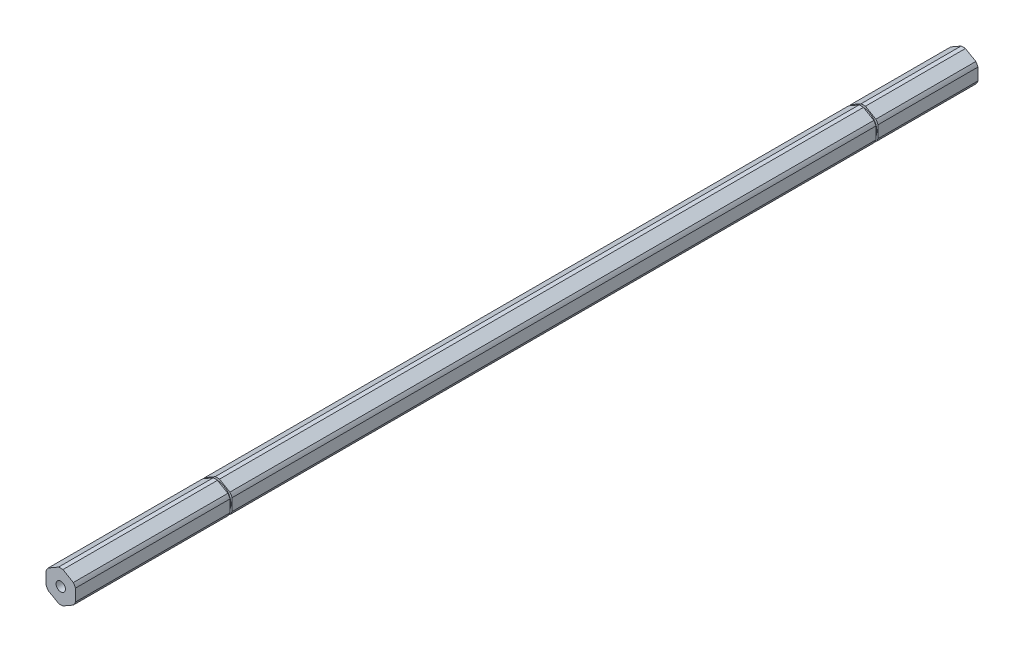
SolidWorks part; units mm, degrees
material "6061-T6 (SS)"
ref_plane "Front Plane" through (0, 0, 0) normal (0, 0, 1) x (1, 0, 0)
ref_plane "Top Plane" through (0, 0, 0) normal (0, 1, 0) x (1, 0, 0)
ref_plane "Right Plane" through (0, 0, 0) normal (1, 0, 0) x (0, 0, -1)
sketch "Sketch1" plane through (0, 0, 0) normal (0, 0, 1) x (1, 0, 0)
  line L1 (0, 7.3323) -> (-6.35, 3.6662)
  line L2 (-6.35, 3.6662) -> (-6.35, -3.6662)
  line L3 (-6.35, -3.6662) -> (0, -7.3323)
  line L4 (0, -7.3323) -> (6.35, -3.6662)
  line L5 (6.35, -3.6662) -> (6.35, 3.6662)
  line L6 (6.35, 3.6662) -> (0, 7.3323)
  circle A0 centre (0, 0) radius 6.35 construction
  circle A1 centre (0, 0) radius 6.858
  dimension "D1" = 12.7
  dimension "D2" = 13.716
extrude "Boss-Extrude1" add sketch "Sketch1" along normal mid plane 388.6403 contours L5 A1 L6 L1 L2 L3 L4 region at (0, 0, 0)
sketch "Sketch2" plane through (0, 0, 194.3202) normal (0, 0, 1) x (1, 0, 0)
  circle A0 centre (0, 0) radius 2.0193
  dimension "D1" = 4.0386
extrude "Cut-Extrude1" [suppressed] cut sketch "Sketch2" against normal through all
sketch "Sketch4" [suppressed] plane through (0, 0, 0) normal (0, 1, 0) x (1, 0, 0)
  line L0 (-2.0193, -194.3202) -> (2.0193, -194.3202) construction
  line L5 (-0.9317, -194.3202) -> (0.9317, -194.3202) construction
  line L7 (9.0297, 151.2672) -> (5.8547, 151.2672)
  line L8 (9.0297, 151.2672) -> (9.0297, 150.3782)
  line L9 (9.0297, 150.3782) -> (5.8547, 150.3782)
  line L10 (5.8547, 151.2672) -> (5.8547, 150.3782)
  line L11 (5.8547, -127.7722) -> (9.0297, -127.7722)
  line L12 (0, 194.3202) -> (0, -194.3202) construction
  line L13 (2.0193, 194.3202) -> (-2.0193, 194.3202) construction
  line L14 (5.8547, -127.7722) -> (5.8547, -126.8832)
  line L15 (5.8547, -126.8832) -> (9.0297, -126.8832)
  line L16 (9.0297, -127.7722) -> (9.0297, -126.8832)
  dimension "D1" = 0.889
  dimension "D2" = 388.6403
  dimension "D3" = 5.8547
  dimension "D4" = 43.053
  dimension "D5" = 3.175
  dimension "D6" = 3.175
  dimension "D7" = 0.889
  dimension "D8" = 66.548
revolve "Cut-Revolve4" [suppressed] cut sketch "Sketch4" angle 360 about L12
hole_wizard "#10-32 Tapped Hole1" positions "3DSketch1" profile "Sketch5" tap size "#10-32" standard "ANSI Inch"
sketch3d "3DSketch1"
  line L0 (0, 0, 194.3202) -> (0, 0, -194.3202) construction
  point P0 (0, 0, 194.3202)
sketch "Sketch5" plane through (0, 0, 194.3202) normal (1, 0, 0) x (0, -1, 0)
  line L0 (0, 0) -> (0, 13.1513)
  line L1 (0, 13.1513) -> (2.0193, 11.938)
  line L2 (2.0193, 11.938) -> (2.0193, 0)
  line L5 (2.0193, 0) -> (0, 0)
  line L10 (0, 13.1513) -> (-2.0193, 11.938) construction
  line L11 (0, -6.35) -> (0, 107.95) construction
  dimension "Tap Drill Dia." = 4.0386
  dimension "Tap Drill Depth" = 11.938
  dimension "Drill Angle" = 118
cosmetic thread "Hole Thread1" parameters "D1"=9.652, "D2"=4.826
sketch "Sketch6" plane through (0, 0, -194.3202) normal (0, 0, -1) x (-1, 0, 0)
  circle A0 centre (0, 0) radius 3.175
  dimension "D1" = 6.35
extrude "Cut-Extrude2" cut sketch "Sketch6" against normal blind 6.35
sketch "Sketch8" plane through (0, 0, 0) normal (0, 1, 0) x (1, 0, 0)
  line L0 (0, 194.3202) -> (0, -194.3202) construction
  line L1 (0.9317, 194.3202) -> (-0.9317, 194.3202) construction
  line L2 (-0.9317, -194.3202) -> (0.9317, -194.3202) construction
  line L4 (5.8547, 151.2672) -> (9.0297, 151.2672)
  line L5 (5.8547, 151.2672) -> (5.8547, 150.3782)
  line L6 (5.8547, 150.3782) -> (9.0297, 150.3782)
  line L7 (9.0297, 151.2672) -> (9.0297, 150.3782)
  line L8 (5.8547, -127.7722) -> (9.0297, -127.7722)
  line L9 (5.8547, -127.7722) -> (5.8547, -126.8832)
  line L10 (5.8547, -126.8832) -> (9.0297, -126.8832)
  line L11 (9.0297, -127.7722) -> (9.0297, -126.8832)
  dimension "D1" = 0.889
  dimension "D2" = 0.889
  dimension "D3" = 3.175
  dimension "D4" = 3.175
  dimension "D5" = 5.8547
  dimension "D6" = 43.053
  dimension "D7" = 66.548
revolve "Cut-Revolve5" cut sketch "Sketch8" angle 360 about L0
equation "\"D1@Boss-Extrude1\"=14.25"
